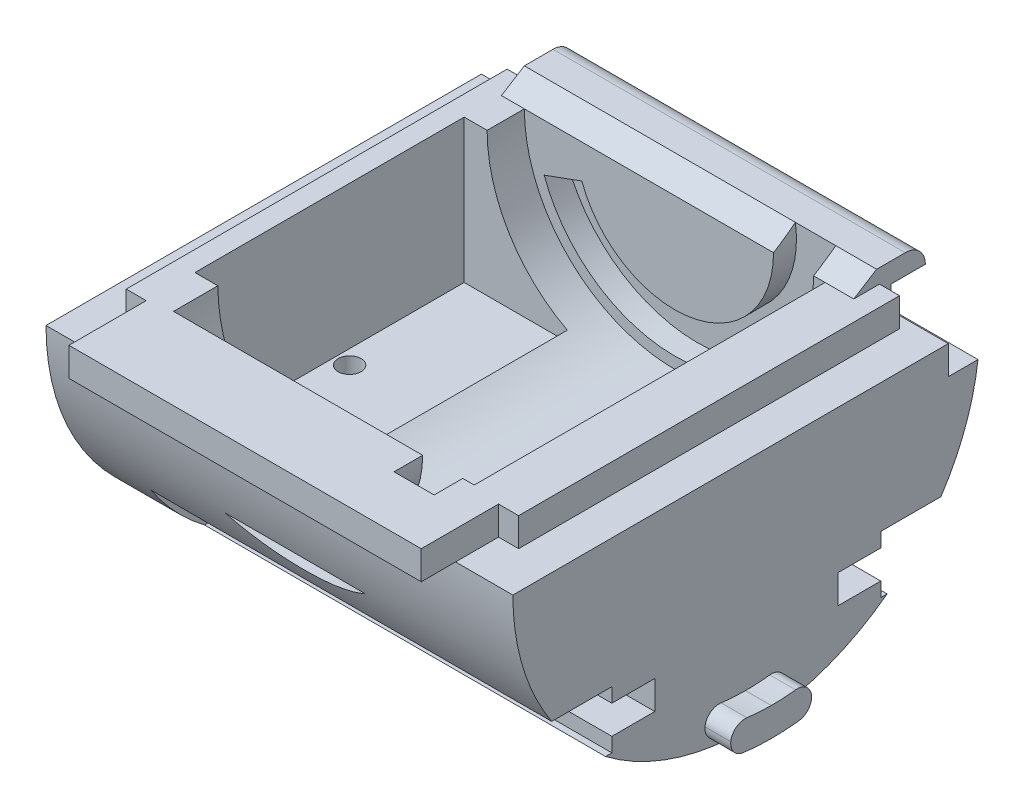
SolidWorks part; units mm, degrees
ref_plane "Front Plane" through (0, 0, 0) normal (0, 0, 1) x (1, 0, 0)
ref_plane "Top Plane" through (0, 0, 0) normal (0, 1, 0) x (1, 0, 0)
ref_plane "Right Plane" through (0, 0, 0) normal (1, 0, 0) x (0, 0, -1)
sketch "Sketch1" plane through (0, 0, 0) normal (0, 1, 0) x (1, 0, 0)
  line L1 (0, 0) -> (41.402, 0)
  line L2 (0, 0) -> (0, -21.971)
  line L3 (0, -21.971) -> (41.402, -21.971)
  line L4 (41.402, 0) -> (41.402, -21.971)
  dimension "D1" = 21.971
  dimension "D2" = 41.402
revolve "Revolve1" add sketch "Sketch1" angle 180 about L1
sketch "Sketch2" plane through (0, 0, 0) normal (0, 1, 0) x (1, 0, 0)
  line L0 (0, 21.971) -> (41.402, 21.971) construction
  line L1 (5.08, 17.145) -> (36.322, 17.145)
  line L2 (5.08, 17.145) -> (5.08, -23.749)
  line L3 (5.08, -23.749) -> (36.322, -23.749)
  line L4 (36.322, 17.145) -> (36.322, -23.749)
  line L6 (41.402, 21.971) -> (41.402, -21.971) construction
  line L7 (0, -21.971) -> (0, 21.971) construction
  line L11 (0, -21.971) -> (41.402, -21.971) construction
  dimension "D1" = 5.08
  dimension "D2" = 5.08
  dimension "D3" = 4.826
  dimension "D4" = 1.778
extrude "Boss-Extrude1" add sketch "Sketch2" along normal blind 2.54
sketch "Sketch3" plane through (0, 2.54, 0) normal (0, 1, 0) x (1, 0, 0)
  line L2 (5.08, 17.145) -> (5.08, -23.749) construction
  line L3 (36.322, -23.749) -> (36.322, 17.145) construction
  line L4 (20.447, 14.605) -> (20.447, -16.51) construction
  line L5 (20.447, 14.605) -> (33.782, 14.605)
  line L6 (33.782, -16.51) -> (20.447, -16.51)
  line L7 (20.447, 14.605) -> (20.447, -16.51)
  line L8 (36.322, 17.145) -> (5.08, 17.145) construction
  line L9 (0, -21.971) -> (5.08, -21.971) construction
  line L12 (7.62, 14.605) -> (7.62, -16.51)
  line L13 (7.62, -16.51) -> (33.782, -16.51)
  line L14 (33.782, -16.51) -> (33.782, 14.605)
  line L15 (33.782, 14.605) -> (7.62, 14.605)
  dimension "D2" = 13.335
  dimension "D1" = 5.461
  dimension "D3" = 2.54
  dimension "D4" = 2.54
  dimension "D5" = 2.54
revolve "Cut-Revolve2" cut sketch "Sketch3" angle 360 about L4
sketch3d "3DSketch1" plane through (0, 0, 0) normal (0, 0, 1) x (1, 0, 0)
  dimension "D1" = 15.875
sketch "Sketch7" plane through (0, 0, -17.145) normal (0, 0, -1) x (-1, 0, 0)
  line L1 (-36.322, 2.54) -> (-5.08, 2.54)
  line L2 (-36.322, 2.54) -> (-36.322, 1.27)
  line L3 (-36.322, 1.27) -> (-5.08, 1.27)
  line L4 (-5.08, 2.54) -> (-5.08, 1.27)
  dimension "D1" = 1.27
extrude "Boss-Extrude5" add sketch "Sketch7" along normal blind 3.81
sketch "Sketch8" plane through (0, 0, 0) normal (0, 1, 0) x (1, 0, 0)
  line L1 (42.164, 20.447) -> (0, 20.447)
  line L2 (42.164, 20.447) -> (42.164, 17.907)
  line L3 (42.164, 17.907) -> (0, 17.907)
  line L4 (0, 20.447) -> (0, 17.907)
  line L5 (36.322, 17.145) -> (5.08, 17.145) construction
  line L7 (36.322, -21.971) -> (36.322, 17.145) construction
  line L8 (0, -21.971) -> (0, 21.971) construction
  dimension "D1" = 5.842
  dimension "D2" = 2.54
  dimension "D3" = 0.762
extrude "Cut-Extrude1" cut sketch "Sketch8" against normal blind 2.54
sketch "Sketch9" plane through (0, 2.54, 0) normal (0, 1, 0) x (1, 0, 0)
  line L0 (5.1158, -6.35) -> (26.6447, -6.35) construction
  line L1 (7.112, -16.51) -> (29.21, -16.51) construction
  line L2 (7.112, 14.605) -> (33.782, 14.605) construction
  line L3 (32.766, 16.637) -> (29.21, 16.637)
  line L4 (32.766, 16.637) -> (32.766, -19.05)
  line L5 (32.766, -19.05) -> (29.21, -19.05)
  line L6 (29.21, 16.637) -> (29.21, -19.05)
  line L7 (36.322, -21.971) -> (36.322, -16.891) construction
  line L8 (20.447, 14.605) -> (20.447, -16.51) construction
  line L9 (33.782, 14.605) -> (32.766, 14.605) construction
  line L11 (0, -21.971) -> (5.08, -21.971) construction
  dimension "D1" = 15.621
  dimension "D2" = 2.54
  dimension "D3" = 2.032
  dimension "D4" = 3.556
  dimension "D5" = 3.556
sketch "Sketch10" plane through (36.322, 0, 0) normal (1, 0, 0) x (0, 0, -1)
  line L0 (-23.749, 2.54) -> (20.955, 2.54) construction
  line L1 (16.891, 0) -> (-16.891, 0)
  line L2 (16.891, 0) -> (16.891, 2.54)
  line L3 (16.891, 2.54) -> (-16.891, 2.54)
  line L4 (-16.891, 0) -> (-16.891, 2.54)
  line L5 (-21.971, 0) -> (17.145, 0) construction
  dimension "D1" = 5.08
  dimension "D2" = 5.08
extrude "Boss-Extrude6" add sketch "Sketch10" along normal blind 1.778
sketch "Sketch13" plane through (0, 2.54, 0) normal (0, 1, 0) x (1, 0, 0)
  line L0 (7.112, -16.51) -> (33.782, -16.51) construction
  line L1 (14.224, -12.573) -> (5.08, -12.573)
  line L2 (14.224, -12.573) -> (14.224, 11.303)
  line L3 (14.224, 11.303) -> (5.08, 11.303)
  line L4 (5.08, -12.573) -> (5.08, 11.303)
  line L5 (33.782, 14.605) -> (7.112, 14.605) construction
  line L7 (5.08, 20.955) -> (5.08, -23.749) construction
  line L8 (7.112, -16.51) -> (7.112, 14.605) construction
  dimension "D1" = 3.937
  dimension "D2" = 3.302
  dimension "D3" = 7.112
sketch "Sketch14" plane through (5.08, 0, 0) normal (-1, 0, 0) x (0, 0, 1)
  line L0 (-20.955, 2.54) -> (23.749, 2.54) construction
  line L1 (-16.891, 2.54) -> (16.891, 2.54)
  line L2 (-16.891, 2.54) -> (-16.891, 0)
  line L3 (-16.891, 0) -> (16.891, 0)
  line L4 (16.891, 2.54) -> (16.891, 0)
  line L5 (16.891, 0) -> (-16.891, 0) construction
  dimension "D1" = 5.08
  dimension "D2" = 5.08
extrude "Boss-Extrude7" add sketch "Sketch14" along normal blind 1.778
extrude "Cut-Extrude3" cut sketch "Sketch13" against normal blind 12.7
sketch "Sketch15" plane through (0, -10.16, 0) normal (0, 1, 0) x (1, 0, 0)
  line L0 (5.08, -12.573) -> (14.224, -12.573) construction
  line L1 (26.037, -12.573) -> (25.021, -12.573)
  line L2 (26.037, -12.573) -> (26.037, 11.303)
  line L3 (26.037, 11.303) -> (25.021, 11.303)
  line L4 (25.021, -12.573) -> (25.021, 11.303)
  line L5 (14.224, 11.303) -> (5.08, 11.303) construction
  line L7 (24.513, 11.303) -> (24.513, -12.573) construction
  dimension "D1" = 0.508
  dimension "D2" = 1.016
sketch "Sketch16" plane through (0, -10.16, 0) normal (0, 1, 0) x (1, 0, 0)
  line L1 (5.08, 11.303) -> (5.08, -12.573) construction
  line L3 (14.224, 11.303) -> (5.08, 11.303) construction
  circle A0 centre (6.35, -0.127) radius 1.016
  dimension "D3" = 2.032
  dimension "D1" = 11.43
  dimension "D2" = 1.27
extrude "Cut-Extrude4" cut sketch "Sketch16" against normal blind 2.54
sketch "Sketch18" plane through (41.402, 0, 0) normal (1, 0, 0) x (0, 0, -1)
  circle A0 centre (-0.0842, -18.9242) radius 1.27
  arc A1 (-21.971, 0) -> (21.971, 0) centre (0, 0) ccw construction
  point P5 (0, -21.971)
  dimension "D2" = 2.54
  dimension "D1" = 3.048
extrude "Boss-Extrude8" add sketch "Sketch18" along normal blind 2.286
sketch "Sketch19" plane through (0, 0, 0) normal (-1, 0, 0) x (0, 0, 1)
  circle A0 centre (0.0842, -18.9242) radius 1.27
  arc A1 (-21.971, 0) -> (21.971, 0) centre (0, 0) ccw construction
  point P5 (0, -21.971)
  dimension "D2" = 2.54
  dimension "D1" = 3.048
extrude "Boss-Extrude9" add sketch "Sketch19" along normal blind 2.286
sketch "Sketch20" plane through (0, 0, -17.145) normal (0, 0, -1) x (-1, 0, 0)
  line L4 (-36.322, 1.27) -> (-36.322, 0)
  line L5 (-36.322, 1.27) -> (-36.322, 0) construction
  line L6 (-36.322, 0) -> (-10.2475, 0)
  line L9 (-10.2475, 0) -> (-5.08, 0)
  line L12 (-5.08, 1.27) -> (-36.322, 1.27)
  line L15 (-5.08, 0) -> (-5.08, 1.27)
extrude "Boss-Extrude10" add sketch "Sketch20" along normal blind 1.27
revolve "Cut-Revolve5" cut sketch "Sketch9" angle 160 about L8 other way angle 160
sketch "x" plane through (43.688, 0, 0) normal (1, 0, 0) x (0, 0, -1)
  line L0 (3.3756, -17.3286) -> (3.6066, -19.8697)
  line L1 (-3.5297, -17.2979) -> (-3.7833, -19.8368)
  arc A0 (-0.0842, -20.1942) -> (3.6066, -19.8697) centre (0, 0) ccw
  circle A1 centre (-0.0842, -18.9242) radius 1.27 construction
  arc A2 (-0.0842, -20.1942) -> (-3.7833, -19.8368) centre (0, 0) cw
  arc A3 (-0.0842, -17.6542) -> (-3.5297, -17.2979) centre (0, 0) cw
  arc A4 (-0.0842, -17.6542) -> (3.3756, -17.3286) centre (0, 0) ccw
  dimension "D1" = 3.81
  dimension "D2" = 3.81
  dimension "D3" = 3.81
  dimension "D4" = 3.81
extrude "Boss-Extrude11" add sketch "x" against normal blind 8.382
sketch "Sketch22" plane through (-2.286, 0, 0) normal (-1, 0, 0) x (0, 0, 1)
  line L0 (-3.3756, -17.3286) -> (-3.6066, -19.8697)
  line L1 (3.7833, -19.8368) -> (3.5297, -17.2979)
  arc A0 (0.0842, -17.6542) -> (3.5297, -17.2979) centre (0, 0) ccw
  circle A1 centre (0.0842, -18.9242) radius 1.27 construction
  arc A2 (0.0842, -17.6542) -> (-3.3756, -17.3286) centre (0, 0) cw
  arc A3 (0.0842, -20.1942) -> (3.7833, -19.8368) centre (0, 0) ccw
  arc A4 (0.0842, -20.1942) -> (-3.6066, -19.8697) centre (0, 0) cw
  dimension "D1" = 3.81
  dimension "D2" = 3.81
  dimension "D3" = 3.81
  dimension "D4" = 3.81
extrude "Boss-Extrude12" add sketch "Sketch22" against normal blind 14.224
fillet "Fillet4" radius 1.27 9 edges at (-1.143, -17.3286, -3.3756) (-1.143, -19.8697, -3.6066) (-1.143, -17.2979, 3.5297) (42.545, -19.8368, 3.7833) (42.545, -17.2979, 3.5297) (42.545, -19.8697, -3.6066) (42.545, -17.3286, -3.3756) (42.545, -17.6542, 0.0729) (-1.143, -19.8368, 3.7833)
sketch "Sketch24" plane through (0, 2.54, 0) normal (0, 1, 0) x (1, 0, 0)
  line L0 (29.21, 16.637) -> (32.766, 16.637) construction
  line L1 (36.322, 20.955) -> (5.08, 20.955)
  line L2 (36.322, 20.955) -> (36.322, 16.637)
  line L3 (36.322, 16.637) -> (5.08, 16.637)
  line L4 (5.08, 20.955) -> (5.08, 16.637)
  dimension "D1" = 0
extrude "Boss-Extrude13" add sketch "Sketch24" along normal blind 1.27
sketch "Sketch23" plane through (36.322, 0, 0) normal (1, 0, 0) x (0, 0, -1)
  line L0 (17.907, 0) -> (17.907, -2.54) construction
  line L1 (18.415, 0) -> (17.907, 0)
  line L2 (18.415, 0) -> (18.415, 1.27)
  line L4 (17.907, 0) -> (17.907, 1.27)
  line L6 (17.907, 1.27) -> (17.907, 2.032)
  line L7 (17.907, 2.032) -> (20.955, 2.032)
  line L8 (20.955, 3.81) -> (20.955, 1.27) construction
  line L9 (20.955, 2.032) -> (20.955, 1.27)
  line L10 (20.955, 1.27) -> (18.415, 1.27)
  dimension "D1" = 0
  dimension "D2" = 0.762
extrude "Cut-Extrude5" cut sketch "Sketch23" against normal blind 40.894
chamfer "Chamfer1" distance 1.27 angle 58 2 edges at (34.544, 2.54, -16.637) (17.145, 2.54, -16.637) first distance on face at (21.1111, -0.1884, -16.637)
fillet "Fillet5" radius 1.778 1 edges at (20.701, 3.81, -20.955)
sketch "Sketch25" plane through (41.402, 0, 0) normal (1, 0, 0) x (0, 0, -1)
  line L1 (20.447, -2.54) -> (17.8567, -2.54)
  line L2 (20.447, -2.54) -> (20.447, 1.778)
  line L3 (20.447, 1.778) -> (17.8567, 1.778)
  line L4 (17.8567, -2.54) -> (17.8567, 1.778)
  line L5 (20.447, 1.778) -> (21.971, 1.778)
  line L6 (20.447, 1.778) -> (20.447, 0)
  line L7 (20.447, 0) -> (21.971, 0)
  line L8 (21.971, 1.778) -> (21.971, 0)
  dimension "D1" = 4.318
  dimension "D2" = 1.778
sketch "Sketch26" plane through (41.402, 0, 0) normal (1, 0, 0) x (0, 0, -1)
  line L0 (21.971, 0) -> (20.447, 0) construction
  line L1 (-21.971, 0) -> (-20.701, 0)
  line L2 (20.701, 0) -> (21.971, 0)
  arc A0 (-21.971, 0) -> (21.971, 0) centre (0, 0) ccw
  arc A1 (-21.971, 0) -> (21.971, 0) centre (0, 0) ccw construction
  arc A2 (-20.701, 0) -> (20.701, 0) centre (0, 0) ccw
  dimension "D1" = 1.27
extrude "Cut-Extrude6" cut sketch "Sketch26" against normal blind 48.26
sketch "Sketch27" plane through (41.402, 0, 0) normal (1, 0, 0) x (0, 0, -1)
  line L0 (-16.891, 0) -> (16.891, 0) construction
  line L1 (-17.2594, -11.43) -> (-11.9254, -11.43)
  line L2 (-17.2594, -11.43) -> (-17.2594, -16.51)
  line L3 (-17.2594, -16.51) -> (-11.9254, -16.51)
  line L4 (-11.9254, -11.43) -> (-11.9254, -12.7)
  line L5 (0, 13.4811) -> (0, -13.4811) construction
  line L6 (17.2594, -16.51) -> (11.9254, -16.51)
  line L7 (11.9254, -11.43) -> (11.9254, -12.7)
  line L8 (17.2594, -11.43) -> (11.9254, -11.43)
  line L9 (17.2594, -11.43) -> (17.2594, -16.51)
  line L10 (-11.9254, -15.24) -> (-11.9254, -16.51)
  line L11 (-11.9254, -12.7) -> (-8.1154, -12.7)
  line L13 (-11.9254, -15.24) -> (-8.1154, -15.24)
  line L14 (-8.1154, -12.7) -> (-8.1154, -15.24)
  line L15 (11.9254, -15.24) -> (11.9254, -16.51)
  line L16 (11.9254, -12.7) -> (8.1154, -12.7)
  line L18 (11.9254, -15.24) -> (8.1154, -15.24)
  line L19 (8.1154, -12.7) -> (8.1154, -15.24)
  arc A0 (-20.701, 0) -> (20.701, 0) centre (0, 0) ccw construction
  dimension "D1" = 5.334
  dimension "D2" = 11.43
  dimension "D3" = 5.08
  dimension "D4" = 2.54
  dimension "D5" = 1.27
  dimension "D6" = 3.81
  dimension "D7" = 3.81
  dimension "D8" = 2.54
  dimension "D9" = 1.27
extrude "Cut-Extrude7" cut sketch "Sketch27" against normal blind 35.56
sketch "Sketch28" plane through (0, -2.54, 0) normal (0, 1, 0) x (1, 0, 0)
  line L0 (41.402, 17.907) -> (41.402, 20.447) construction
  line L1 (41.402, 19.177) -> (0, 19.177)
  line L2 (41.402, 19.177) -> (41.402, 24.7565)
  line L3 (41.402, 24.7565) -> (0, 24.7565)
  line L4 (0, 19.177) -> (0, 24.7565)
extrude "Cut-Extrude8" cut sketch "Sketch28" along normal blind 3.81
